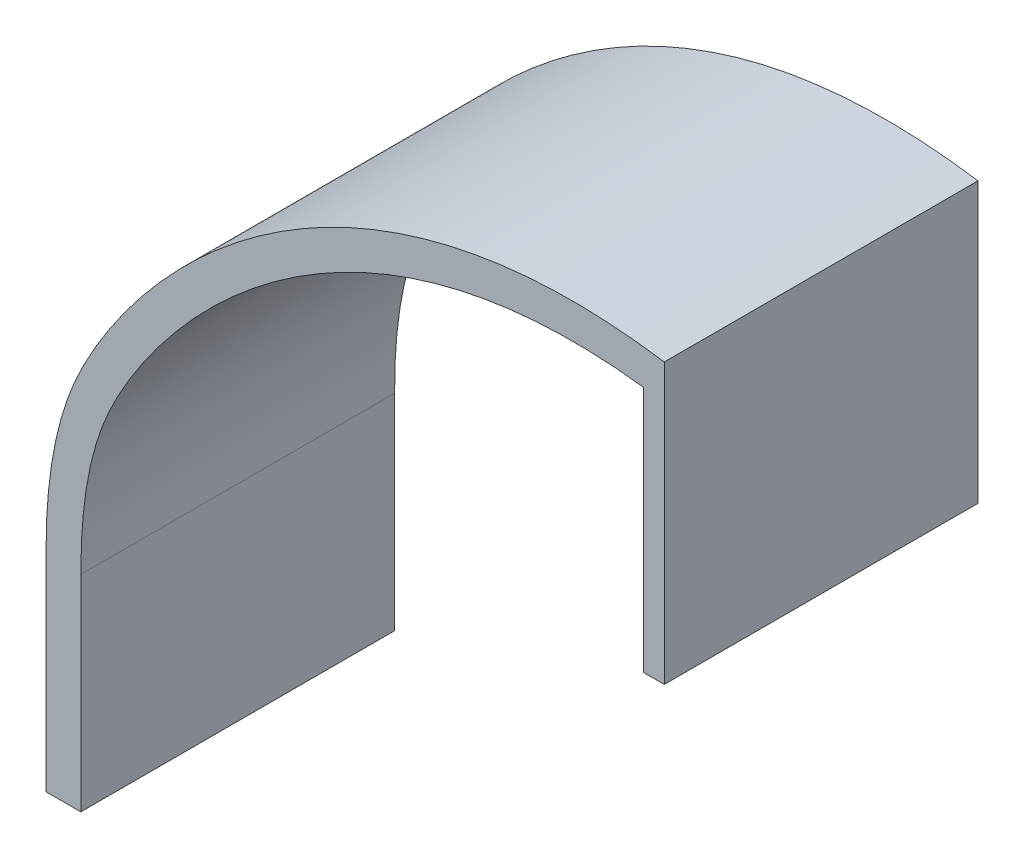
SolidWorks part; units mm, degrees
material "Aluminum Bronze"
ref_plane "Front Plane" through (0, 0, 0) normal (0, 0, 1) x (1, 0, 0)
ref_plane "Top Plane" through (0, 0, 0) normal (0, 1, 0) x (1, 0, 0)
ref_plane "Right Plane" through (0, 0, 0) normal (1, 0, 0) x (0, 0, -1)
sketch "Sketch1" plane through (0, 0, 0) normal (0, 0, 1) x (1, 0, 0)
  line L0 (0, 0) -> (0, 10)
  line L1 (0, 10) -> (0, 49) construction
  line L2 (0, 49) -> (103.68, 49) construction
  line L3 (103.68, 49) -> (103.68, 99) construction
  line L4 (83.68, 49) -> (83.68, 99) construction
  dimension "D1" = 10
  dimension "D3" = 103.68
  dimension "D4" = 50
  dimension "D2" = 49
  dimension "D5" = 20
sketch "Sketch2" plane through (0, 0, 0) normal (0, 0, 1) x (1, 0, 0)
  line L1 (0, 0) -> (0, 10) construction
  line L4 (0, 49) -> (103.68, 49) construction
  line L5 (0, 0) -> (0, 29.5)
  line L7 (0, 26.9474) -> (0, -6.9479) construction
  line L8 (-5, 0) -> (-5, 29.5)
  line L10 (-5, 0) -> (0, 0)
  line L11 (0, 10) -> (0, 49) construction
  line L15 (83.68, 49) -> (83.68, 99) construction
  line L17 (83.68, 97.7268) -> (80.68, 97.7268)
  line L18 (83.68, 97.7268) -> (83.68, 57.6669)
  line L19 (83.68, 57.6669) -> (80.68, 57.6669)
  line L20 (80.68, 97.7268) -> (80.68, 57.6669)
  spline S0 degree 3 poles (0, 29.5) (0, 33.6564) (0.252, 42.1955) (8.5017, 63.8076) (38.7642, 99.837) (83.68, 92.6669) knots 0 0 0 0 0.310313 0.410313 1 1 1 1
  spline S1 degree 1 poles (-5, 29.5) (84.4682, 97.6043) knots 0 0 1 1 construction
  spline S2 degree 3 poles (-5, 29.5) (-5, 29.7239) (-4.999, 30.1619) (-4.9912, 31.1158) (-4.9673, 32.3931) (-4.9051, 34.0631) (-4.763, 36.4474) (-4.4475, 39.6897) (-3.7534, 43.906) (-2.6633, 48.3095) (-1.0205, 52.935) (1.6426, 58.2335) (5.5553, 64.3844) (10.7274, 70.9986) (17.1994, 77.7286) (25.0006, 84.1867) (34.1591, 89.9741) (44.6895, 94.6743) (54.5994, 97.3302) (63.1885, 98.4896) (69.9506, 98.8273) (75.8555, 98.6242) (80.3987, 98.1823) (82.6922, 97.876) (83.9418, 97.6873) (84.2733, 97.6355) (84.4682, 97.6043) knots 0 0 0 0 0.015625 0.03125 0.0625 0.09375 0.125 0.1875 0.25 0.3125 0.375 0.4375 0.5 0.5625 0.625 0.6875 0.75 0.8125 0.875 0.90625 0.9375 0.96875 0.984375 0.995907 0.997544 1 1 1 1
  point P9 (0, 0)
  point P10 (7.9528, 49)
  point P11 (4.1543, 49)
  point P17 (83.68, 87.8423)
  point P18 (83.68, 92.6669)
  point P19 (0, 0)
  point P20 (2.9139, 49)
  dimension "D2" = 35
  dimension "D3" = 3
  dimension "D1" = 5
extrude "Boss-Extrude1" add sketch "Sketch2" along normal mid plane 45 contours S2 L8 L10 L5 S0 L20 L17 | L18 L17 L20 L19 region at (-2.5, 1.3271, 0)
sketch "Sketch3" plane through (0, 0, 0) normal (0, 0, 1) x (1, 0, 0)
  line L0 (80.68, 93.0934) -> (80.68, 57.6669) construction
  line L1 (80.68, 93.0934) -> (80.68, 57.6669)
  line L2 (80.68, 75.3801) -> (53.3318, 91.707)
  spline S0 degree 3 poles (-1495.0656, 2629.2066) (171.6476, -75.7354) (-25.0767, -24.1585) (23.6846, 103.5825) (375.2468, 442.5384) (1093.3973, -2708.0655) knots -3.070225 -3.070225 -3.070225 -3.070225 0.310313 0.410313 2.840401 2.840401 2.840401 2.840401 only from (0, 29.5) to (80.68, 93.0934) construction
  spline S1 degree 3 poles (0, 29.5) (0, 33.6564) (0.252, 42.1955) (8.3924, 63.5211) (37.6101, 98.4599) (80.68, 93.0934) knots 0 0 0 0 0.310313 0.410313 0.986745 0.986745 0.986745 0.986745
  spline S2 degree 3 poles (74.6438, 83.2508) (58.8684, 91.4087) (76.5485, 93.2939) (80.1824, 81.9827) (74.6438, 83.2508) (58.8684, 91.4087) (76.5485, 93.2939) knots -0.658817 -0.451499 -0.385618 0 0.341183 0.548501 0.614382 1 1.341183 1.548501 1.614382 only from (65.9282, 90.1733) to (65.9282, 90.1733)
  point P7 (76.3206, 89.2285)
  point P9 (0, 0)
  point P10 (65.9282, 90.1733)
  point P11 (0, 0)
extrude "Boss-Extrude2" add sketch "Sketch3" along normal mid plane 5 contours S1 L2 L1 S2 region at (80.3506, 84.2368, 0)
equation "\"D5@Sketch1\"=20"
